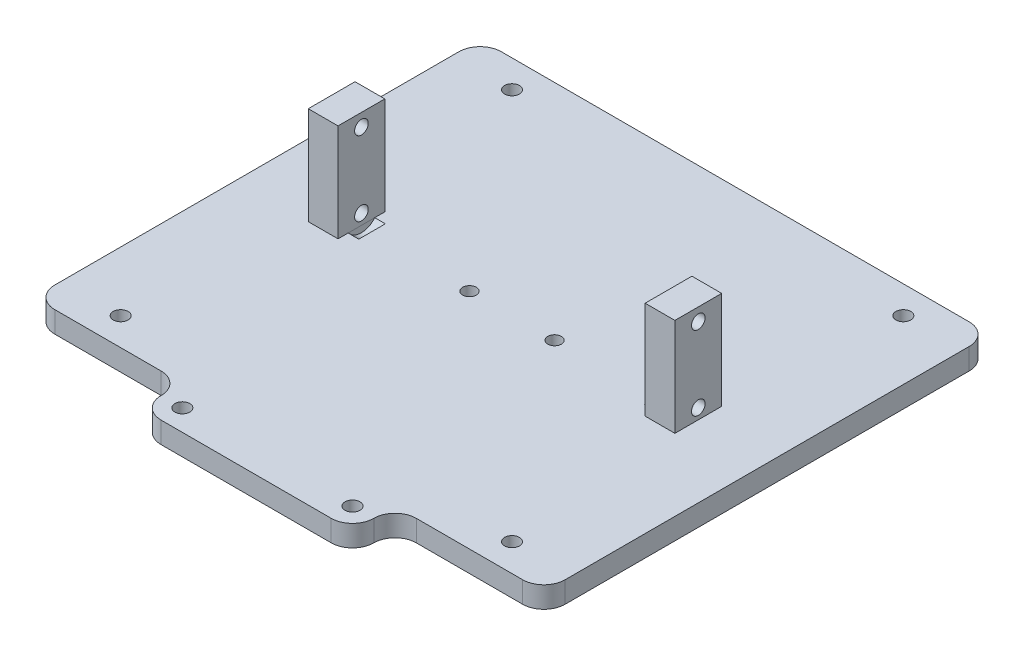
SolidWorks part; units mm, degrees
ref_plane "정면" through (0, 0, 0) normal (0, 0, 1) x (1, 0, 0)
ref_plane "윗면" through (0, 0, 0) normal (0, 1, 0) x (1, 0, 0)
ref_plane "우측면" through (0, 0, 0) normal (1, 0, 0) x (0, 0, -1)
sketch "스케치1" plane through (0, 0, 0) normal (0, 1, 0) x (1, 0, 0)
  line L0 (-25, -52.5) -> (-60, -52.5)
  line L1 (60, 52.5) -> (-60, 52.5)
  line L2 (60, 52.5) -> (60, -52.5)
  line L3 (60, -52.5) -> (25, -52.5)
  line L4 (-60, 52.5) -> (-60, -52.5)
  line L5 (60, 52.5) -> (-60, -52.5) construction
  line L6 (60, -52.5) -> (-60, 52.5) construction
  line L7 (25, -62.5) -> (-25, -62.5)
  line L8 (25, -62.5) -> (25, -52.5)
  line L10 (-25, -62.5) -> (-25, -52.5)
  line L11 (25, -62.5) -> (-25, -52.5) construction
  line L12 (25, -52.5) -> (-25, -62.5) construction
  point P0 (0, 0)
  point P6 (0, -57.5)
  dimension "D1" = 120
  dimension "D2" = 105
  dimension "D3" = 50
  dimension "D4" = 10
extrude "보스-돌출1" add sketch "스케치1" along normal blind 5
fillet "필렛1" radius 5 8 edges at (60, 2.5, -52.5) (60, 2.5, 52.5) (-60, 2.5, -52.5) (-60, 2.5, 52.5) (-25, 2.5, 52.5) (25, 2.5, 52.5) (25, 2.5, 62.5) (-25, 2.5, 62.5)
sketch "스케치2" plane through (0, 5, 0) normal (0, 1, 0) x (1, 0, 0)
  line L0 (-43.1, 29.5) -> (-43.1, -5.3) construction
  line L1 (-36.1, -4.8) -> (-43.1, -4.8)
  line L2 (-36.1, -4.8) -> (-36.1, 6.2)
  line L3 (-36.1, 6.2) -> (-43.1, 6.2)
  line L4 (-43.1, -4.8) -> (-43.1, 6.2)
  line L5 (-61.9, -0.8) -> (-43.1, -0.8) construction
  line L6 (-43.1, 2.2) -> (-61.9, 2.2) construction
  dimension "D1" = 7
  dimension "D2" = 4
  dimension "D3" = 4
extrude "보스-돌출2" add sketch "스케치2" along normal blind 23 separate body
sketch "스케치3" plane through (-36.1, 0, 0) normal (1, 0, 0) x (0, 0, -1)
  circle A0 centre (0.7, 7.5) radius 1.5 construction
  circle A1 centre (0.7, 25) radius 1.5 construction
  circle A2 centre (0.7, 25) radius 1.6
  circle A3 centre (0.7, 7.5) radius 1.6
  circle A4 centre (0.7, 7.5) radius 1.5 construction
  circle A5 centre (0.7, 25) radius 1.5 construction
  dimension "D1" = 3.2
  dimension "D2" = 3.2
extrude "컷-돌출1" cut sketch "스케치3" against normal through all
mirror "대칭 복사1" about plane through (0, 0, 0) normal (1, 0, 0) of bodies 103
sketch "스케치5" plane through (0, 5, 0) normal (0, 1, 0) x (1, 0, 0)
  circle A0 centre (-46, -46) radius 1.75 construction
  circle A1 centre (-46, 46) radius 1.75 construction
  circle A2 centre (46, 46) radius 1.75 construction
  circle A3 centre (46, -46) radius 1.75 construction
  circle A4 centre (-46, -46) radius 1.75
  circle A5 centre (-46, 46) radius 1.75
  circle A6 centre (46, 46) radius 1.75
  circle A7 centre (46, -46) radius 1.75
extrude "컷-돌출3" cut sketch "스케치5" against normal through all
sketch "스케치6" plane through (0, 5, 0) normal (0, 1, 0) x (1, 0, 0)
  circle A0 centre (20, -57.5) radius 1.75 construction
  circle A1 centre (-20, -57.5) radius 1.75 construction
  circle A2 centre (20, -57.5) radius 1.75
  circle A3 centre (-20, -57.5) radius 1.75
extrude "컷-돌출4" cut sketch "스케치6" against normal through all
sketch "Sketch2" plane through (36.1, 0, 0) normal (-1, 0, 0) x (0, 0, 1)
  circle A0 centre (-0.7, 7.5) radius 4
  dimension "D1" = 8
extrude "Cut-Extrude1" cut sketch "Sketch2" along normal blind 2.5
sketch "Sketch3" plane through (-36.1, 0, 0) normal (1, 0, 0) x (0, 0, -1)
  circle A0 centre (0.7, 7.5) radius 4
  dimension "D1" = 8
extrude "Cut-Extrude2" cut sketch "Sketch3" along normal blind 2.5
sketch "Sketch4" plane through (0, 5, 0) normal (0, 1, 0) x (1, 0, 0)
  circle A0 centre (10, 0) radius 1.5 construction
  circle A1 centre (-10, 0) radius 1.5 construction
  circle A2 centre (10, 0) radius 1.5 construction
  circle A3 centre (-10, 0) radius 1.5 construction
  circle A4 centre (-10, 0) radius 1.6
  circle A5 centre (10, 0) radius 1.6
  dimension "D1" = 3.2
  dimension "D2" = 3.2
extrude "Cut-Extrude3" cut sketch "Sketch4" against normal through all and the other way through all
